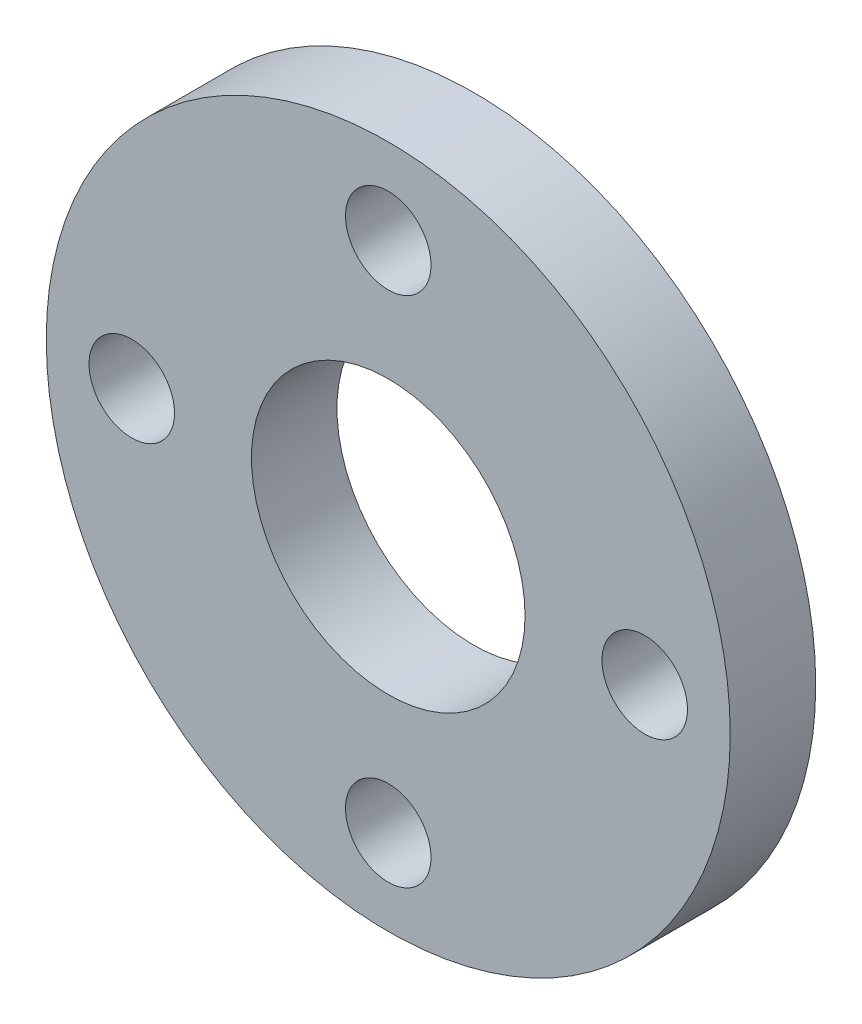
SolidWorks part; units mm, degrees
material "Pine"
ref_plane "Front Plane" through (0, 0, 0) normal (0, 0, 1) x (1, 0, 0)
ref_plane "Top Plane" through (0, 0, 0) normal (0, 1, 0) x (1, 0, 0)
ref_plane "Right Plane" through (0, 0, 0) normal (1, 0, 0) x (0, 0, -1)
sketch "Sketch1" plane through (0, 0, 0) normal (0, 0, 1) x (1, 0, 0)
  circle A0 centre (0, 228.6) radius 10.16
  circle A1 centre (0, 228.6) radius 25.4
  circle A3 centre (0, 247.65) radius 3.175
  circle A4 centre (19.05, 228.6) radius 3.175
  circle A5 centre (0, 209.55) radius 3.175
  circle A6 centre (-19.05, 228.6) radius 3.175
  circle A7 centre (0, 228.6) radius 12.7 construction
  point P4 (4.0322, 227.9756)
  point P9 (-4.6291, 225.075)
  point P11 (-12.2635, 243.1777)
  point P18 (0, 228.6)
  dimension "D1" = 19.05
  dimension "D2" = 50.8
  dimension "D3" = 6.35
  dimension "D5" = 20.32
  dimension "D4" = 4
extrude "Boss-Extrude1" add sketch "Sketch1" along normal blind 6.35
